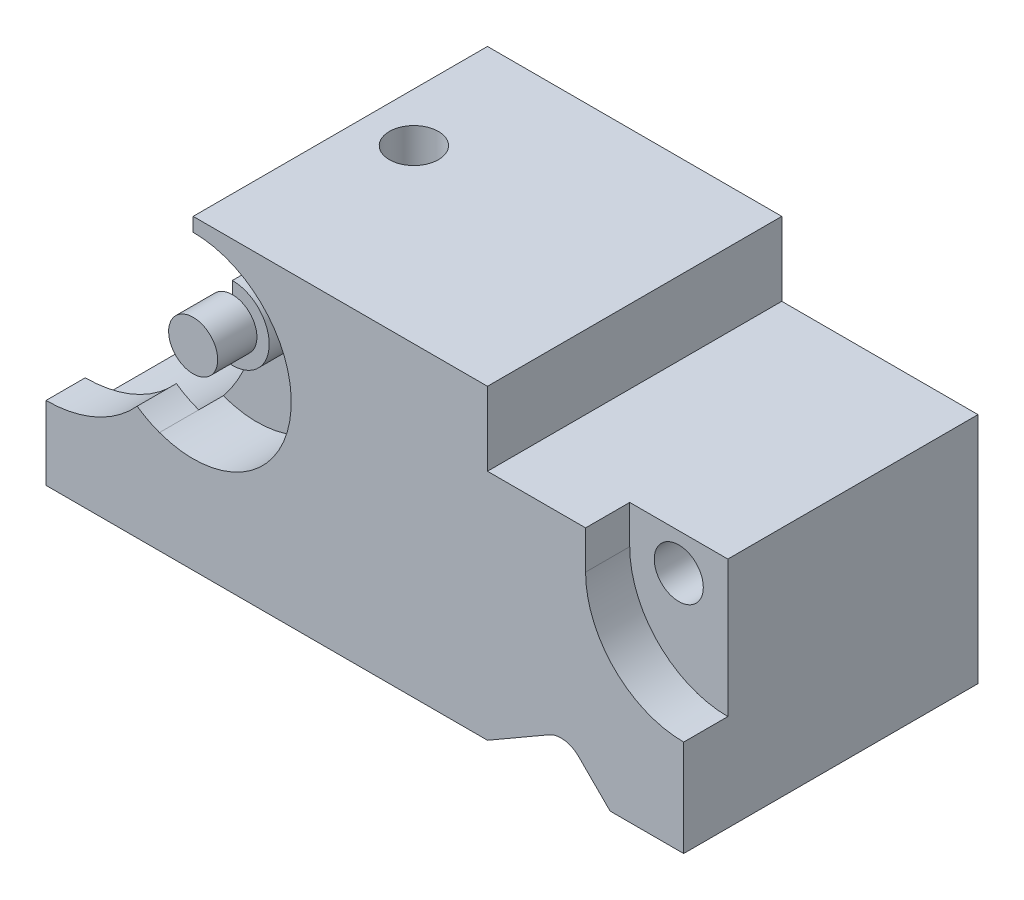
SolidWorks part; units mm, degrees
ref_plane "Front Plane" through (0, 0, 0) normal (0, 0, 1) x (1, 0, 0)
ref_plane "Top Plane" through (0, 0, 0) normal (0, 1, 0) x (1, 0, 0)
ref_plane "Right Plane" through (0, 0, 0) normal (1, 0, 0) x (0, 0, -1)
sketch "Sketch1" plane through (0, 0, 0) normal (0, 0, 1) x (1, 0, 0)
  line L0 (-65, 9.9984) -> (-65, 0)
  line L1 (-65, 0) -> (65, 0)
  line L2 (65, 0) -> (65, 47.5)
  line L3 (65, 47.5) -> (25, 47.5)
  line L4 (25, 47.5) -> (25, 62.5)
  line L5 (25, 62.5) -> (-35, 62.5)
  line L6 (-35, 62.5) -> (-35, 39.6863)
  arc A1 (-35, 39.6863) -> (-65, 9.9984) centre (-65, 40) cw
  point P0 (0, 0)
  dimension "D2" = 30.0016
  dimension "D1" = 40
  dimension "D3" = 47.5
  dimension "D4" = 15
  dimension "D5" = 30
  dimension "D6" = 40
  dimension "D7" = 60
  dimension "D8" = 9.9984
extrude "Boss-Extrude1" add sketch "Sketch1" along normal blind 30 and the other way blind 30
sketch "Sketch2" plane through (0, 0, 30) normal (0, 0, 1) x (1, 0, 0)
  line L0 (-35, 59.6863) -> (-35.0014, 39.7135)
  arc A0 (-41.8648, 20.9013) -> (-35, 59.6863) centre (-35, 39.6863) ccw
  arc A1 (-41.8648, 20.9013) -> (-35.0014, 39.7135) centre (-65, 40) ccw
  dimension "D2" = 40
extrude "Cut-Extrude1" cut sketch "Sketch2" against normal blind 13
sketch "Sketch3" plane through (0, 0, 30) normal (0, 0, 1) x (1, 0, 0)
  line L0 (-65, 9.9984) -> (-65, 15)
  arc A0 (-65, 15) -> (-46.4237, 23.2692) centre (-65, 40) ccw
  arc A2 (-65, 9.9984) -> (-41.8635, 20.9003) centre (-65, 40) ccw
  arc A5 (-46.4237, 23.2692) -> (-41.8635, 20.9003) centre (-35, 39.6863) ccw
  point P3 (0, 0)
  point P6 (0, 0)
  dimension "D1" = 25
  dimension "D2" = 30.0016
extrude "Boss-Extrude2" add sketch "Sketch3" against normal blind 8
sketch "Sketch4" plane through (0, 0, 17) normal (0, 0, 1) x (1, 0, 0)
  line L0 (-35, 47.1863) -> (-35, 39.6863)
  arc A0 (-35.9375, 32.2451) -> (-35, 47.1863) centre (-35, 39.6863) ccw
  arc A1 (-35.9375, 32.2451) -> (-35, 39.6863) centre (-65, 39.6863) ccw
  dimension "D1" = 15
  dimension "D2" = 60
extrude "Boss-Extrude3" add sketch "Sketch4" along normal blind 5
sketch "Sketch5" plane through (0, 0, 22) normal (0, 0, 1) x (1, 0, 0)
  circle A0 centre (-35, 39.6863) radius 5
  dimension "D1" = 10
extrude "Boss-Extrude4" add sketch "Sketch5" along normal blind 8
sketch "Sketch6" plane through (0, 0, 30) normal (0, 0, 1) x (1, 0, 0)
  line L0 (-35, 39.6863) -> (74.5113, 39.6863) construction
  line L1 (65, 47.5) -> (45, 47.5)
  line L2 (65, 47.5) -> (25, 47.5) construction
  line L3 (45, 47.5) -> (45, 39.6863)
  line L4 (65, 47.5) -> (65, 39.6863)
  line L5 (65, 0) -> (65, 47.5) construction
  line L6 (65, 19.6863) -> (65, 39.6863)
  arc A0 (45, 39.6863) -> (65, 19.6863) centre (65, 39.6863) ccw
  dimension "D1" = 20
extrude "Cut-Extrude2" cut sketch "Sketch6" against normal blind 9
sketch "Sketch7" plane through (0, 0, 21) normal (0, 0, 1) x (1, 0, 0)
  line L1 (65, 19.6863) -> (65, 47.5) construction
  line L2 (-65, 0) -> (65, 0) construction
  circle A0 centre (55, 40) radius 5
  point P2 (0, 0)
  point P5 (0, 0)
  dimension "D1" = 10
  dimension "D2" = 10
  dimension "D3" = 40
extrude "Cut-Extrude3" cut sketch "Sketch7" against normal through all
sketch "Sketch8" plane through (0, 62.5, 0) normal (0, 1, 0) x (1, 0, 0)
  line L0 (-65, 30) -> (-65, -22) construction
  line L1 (25, -30) -> (-35, -30) construction
  circle A0 centre (-25, 5) radius 5
  dimension "D1" = 10
  dimension "D2" = 40
  dimension "D3" = 35
extrude "Cut-Extrude4" cut sketch "Sketch8" against normal through all
sketch "Sketch9" plane through (0, 0, 30) normal (0, 0, 1) x (1, 0, 0)
  line L0 (25, 0) -> (50, 0)
  line L1 (-65, 0) -> (65, 0) construction
  line L2 (25, 0) -> (37.5267, 7.2323)
  line L3 (43.5623, 6.4377) -> (50, 0)
  arc A0 (43.5623, 6.4377) -> (37.5267, 7.2323) centre (40.0267, 2.9022) ccw
  dimension "D5" = 5
  dimension "D1" = 25
  dimension "D2" = 15
  dimension "D3" = 30
  dimension "D4" = 45
extrude "Cut-Extrude5" cut sketch "Sketch9" against normal through all
